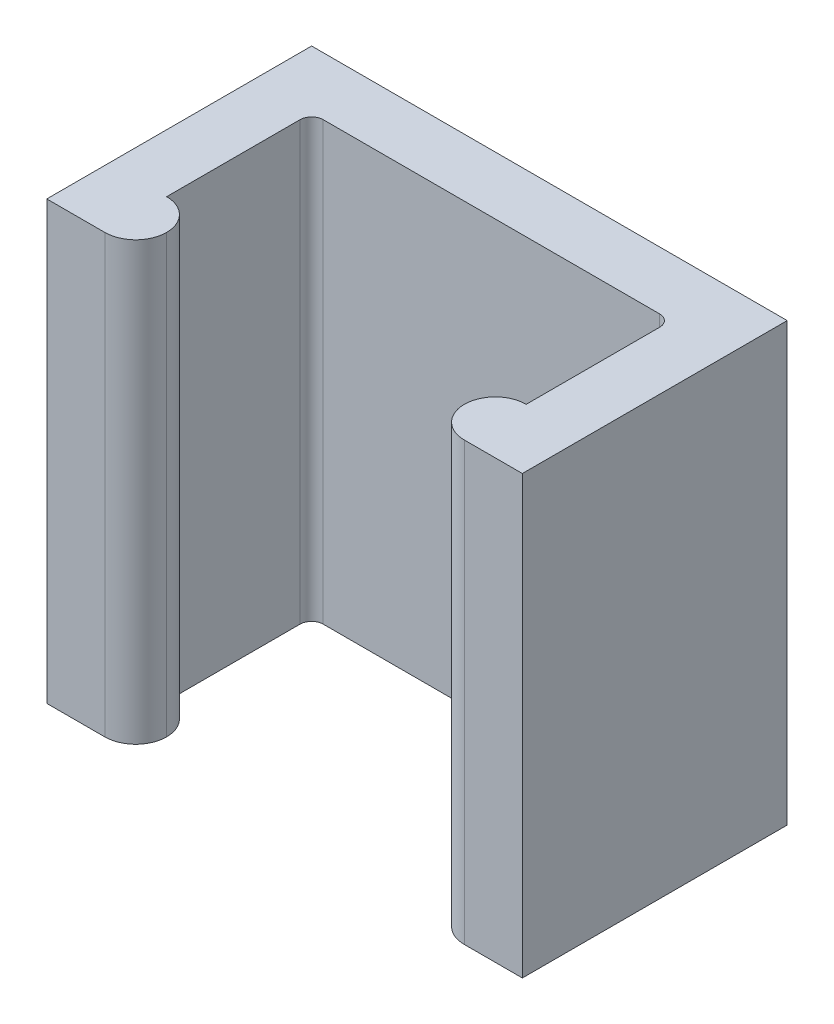
SolidWorks part; units mm, degrees
ref_plane "정면" through (0, 0, 0) normal (0, 0, 1) x (1, 0, 0)
ref_plane "윗면" through (0, 0, 0) normal (0, 1, 0) x (1, 0, 0)
ref_plane "우측면" through (0, 0, 0) normal (1, 0, 0) x (0, 0, -1)
sketch "스케치1" plane through (0, 0, 0) normal (0, 0, 1) x (1, 0, 0)
  line L1 (-6.15, -5.65) -> (6.15, -5.65)
  line L2 (-6.15, -5.65) -> (-6.15, 5.65)
  line L3 (-6.15, 5.65) -> (6.15, 5.65)
  line L4 (6.15, -5.65) -> (6.15, 5.65)
  line L5 (-6.15, -5.65) -> (6.15, 5.65) construction
  line L6 (-6.15, 5.65) -> (6.15, -5.65) construction
  point P0 (0, 0)
  dimension "D1" = 12.3
  dimension "D2" = 11.3
extrude "보스-돌출1" add sketch "스케치1" along normal blind 2.5
sketch "스케치2" plane through (0, 0, 2.5) normal (0, 0, 1) x (1, 0, 0)
  line L0 (-6.15, -5.65) -> (6.15, -5.65) construction
  line L1 (-6.15, 5.65) -> (-4.65, 5.65)
  line L2 (-6.15, 5.65) -> (-6.15, -5.65)
  line L3 (-6.15, -5.65) -> (-4.65, -5.65)
  line L4 (-4.65, 5.65) -> (-4.65, -5.65)
  line L6 (6.15, 5.65) -> (4.65, 5.65)
  line L7 (6.15, 5.65) -> (6.15, -5.65)
  line L8 (6.15, -5.65) -> (4.65, -5.65)
  line L9 (4.65, 5.65) -> (4.65, -5.65)
  dimension "D1" = 1.5
  dimension "D2" = 1.5
extrude "보스-돌출2" add sketch "스케치2" along normal blind 4.35
sketch "스케치5" plane through (0, 0, 2.5) normal (0, 0, 1) x (1, 0, 0)
  line L0 (4.65, 5.65) -> (4.65, -5.65) construction
  line L1 (-4.65, -5.75) -> (4.65, -5.75)
  line L2 (-4.65, -5.75) -> (-4.65, 5.75)
  line L3 (-4.65, 5.75) -> (4.65, 5.75)
  line L4 (4.65, -5.75) -> (4.65, 5.75)
  line L5 (-4.65, -5.75) -> (4.65, 5.75) construction
  line L6 (-4.65, 5.75) -> (4.65, -5.75) construction
  point P0 (0, 0)
  dimension "D1" = 11.5
extrude "컷-돌출1" cut sketch "스케치5" against normal blind 1
sketch "스케치8" plane through (-4.65, 0, 0) normal (1, 0, 0) x (0, 0, -1)
  line L0 (-6.85, -5.65) -> (-1.5, -5.65) construction
  line L1 (-6.85, 5.65) -> (-5.25, 5.65)
  line L2 (-6.85, 5.65) -> (-6.85, -5.65)
  line L3 (-6.85, -5.65) -> (-5.25, -5.65)
  line L4 (-5.25, 5.65) -> (-5.25, -5.65)
  dimension "D1" = 1.6
extrude "보스-돌출5" add sketch "스케치8" along normal blind 0.8
sketch "스케치9" plane through (4.65, 0, 0) normal (-1, 0, 0) x (0, 0, 1)
  line L0 (6.85, 5.65) -> (1.5, 5.65) construction
  line L1 (6.85, -5.65) -> (5.25, -5.65)
  line L2 (6.85, -5.65) -> (6.85, 5.65)
  line L3 (6.85, 5.65) -> (5.25, 5.65)
  line L4 (5.25, -5.65) -> (5.25, 5.65)
  dimension "D1" = 1.6
extrude "보스-돌출6" add sketch "스케치9" along normal blind 0.8
fillet "필렛7" radius 0.8 4 edges at (3.85, 0, 6.85) (-3.85, 0, 6.85) (3.85, 0, 5.25) (-3.85, 0, 5.25)
fillet "필렛8" radius 0.3 2 edges at (4.65, 0, 1.5) (-4.65, 0, 1.5)
